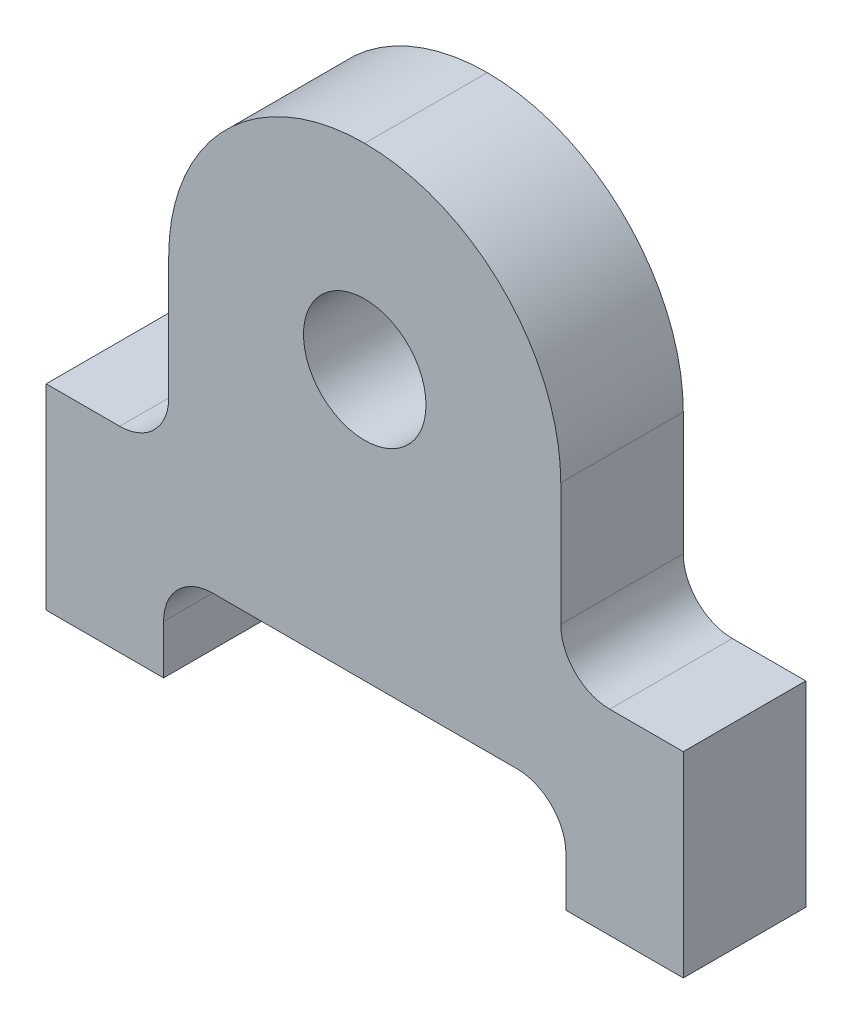
SolidWorks part; units mm, degrees
ref_plane "Front Plane" through (0, 0, 0) normal (0, 0, 1) x (1, 0, 0)
ref_plane "Top Plane" through (0, 0, 0) normal (0, 1, 0) x (1, 0, 0)
ref_plane "Right Plane" through (0, 0, 0) normal (1, 0, 0) x (0, 0, -1)
sketch "Sketch1" plane through (0, 0, 0) normal (0, 0, 1) x (1, 0, 0)
  line L1 (16.51, -14.605) -> (-16.51, -14.605)
  line L2 (16.51, -14.605) -> (16.51, 14.605)
  line L3 (16.51, 14.605) -> (-16.51, 14.605)
  line L4 (-16.51, -14.605) -> (-16.51, 14.605)
  line L5 (16.51, -14.605) -> (-16.51, 14.605) construction
  line L6 (16.51, 14.605) -> (-16.51, -14.605) construction
  point P0 (0, 0)
  dimension "D1" = 33.02
  dimension "D2" = 29.21
extrude "Boss-Extrude1" add sketch "Sketch1" along normal blind 6.35
sketch "Sketch2" plane through (0, 0, 6.35) normal (0, 0, 1) x (1, 0, 0)
  line L0 (-16.51, -4.445) -> (16.51, -4.445) construction
  line L1 (-16.51, 14.605) -> (-16.51, -14.605) construction
  line L2 (16.51, -14.605) -> (16.51, 14.605) construction
  line L3 (-16.51, -14.605) -> (16.51, -14.605) construction
  line L4 (-16.51, -9.525) -> (16.51, -9.525) construction
  line L5 (-16.51, -4.445) -> (-16.51, -14.605)
  line L6 (-10.4267, -14.605) -> (10.4267, -14.605) construction
  line L7 (-10.4267, -14.605) -> (-10.4267, -9.525)
  line L8 (-10.4267, -9.525) -> (10.4267, -9.525)
  line L9 (10.4267, -14.605) -> (10.4267, -9.525)
  line L10 (-16.51, -14.605) -> (-10.4267, -14.605)
  line L11 (16.51, -4.445) -> (16.51, -14.605)
  line L12 (16.51, -14.605) -> (10.4267, -14.605)
  line L13 (16.51, 14.605) -> (-16.51, 14.605) construction
  line L14 (-10.16, 14.605) -> (10.16, 14.605)
  line L15 (-10.16, 14.605) -> (-10.16, -4.445)
  line L16 (-10.16, -4.445) -> (10.16, -4.445) construction
  line L17 (10.16, 14.605) -> (10.16, -4.445)
  line L18 (-16.51, -4.445) -> (-10.16, -4.445)
  line L19 (10.16, -4.445) -> (16.51, -4.445)
  circle A0 centre (0, 4.445) radius 3.175
  point P17 (0, -9.525)
  point P28 (0, 14.605)
  dimension "D2" = 6.35
  dimension "D1" = 10.16
  dimension "D3" = 19.05
  dimension "D4" = 5.08
  dimension "D5" = 20.8534
  dimension "D6" = 20.32
sketch "Sketch3" plane through (0, 0, 6.35) normal (0, 0, 1) x (1, 0, 0)
  line L1 (-16.51, 14.605) -> (-10.16, 14.605)
  line L2 (-16.51, 14.605) -> (-16.51, -4.445)
  line L3 (-16.51, -4.445) -> (-10.16, -4.445)
  line L4 (-10.16, 14.605) -> (-10.16, -4.445)
  line L5 (10.16, 14.605) -> (16.51, 14.605)
  line L6 (10.16, 14.605) -> (10.16, -4.445)
  line L7 (10.16, -4.445) -> (16.51, -4.445)
  line L8 (16.51, 14.605) -> (16.51, -4.445)
  line L9 (-10.4267, -9.525) -> (10.4267, -9.525)
  line L10 (-10.4267, -9.525) -> (-10.4267, -14.605)
  line L11 (-10.4267, -14.605) -> (10.4267, -14.605)
  line L12 (10.4267, -9.525) -> (10.4267, -14.605)
  circle A0 centre (0, 4.445) radius 3.175
extrude "Cut-Extrude1" cut sketch "Sketch3" against normal up to next
fillet "Fillet1" radius 10.16 2 edges at (10.16, 14.605, 3.175) (-10.16, 14.605, 3.175)
fillet "Fillet2" radius 2.54 4 edges at (10.16, -4.445, 3.175) (-10.16, -4.445, 3.175) (10.4267, -9.525, 3.175) (-10.4267, -9.525, 3.175)
ref_axis "Axis1" through (0, 4.445, 0) along (0, 0, 1)
